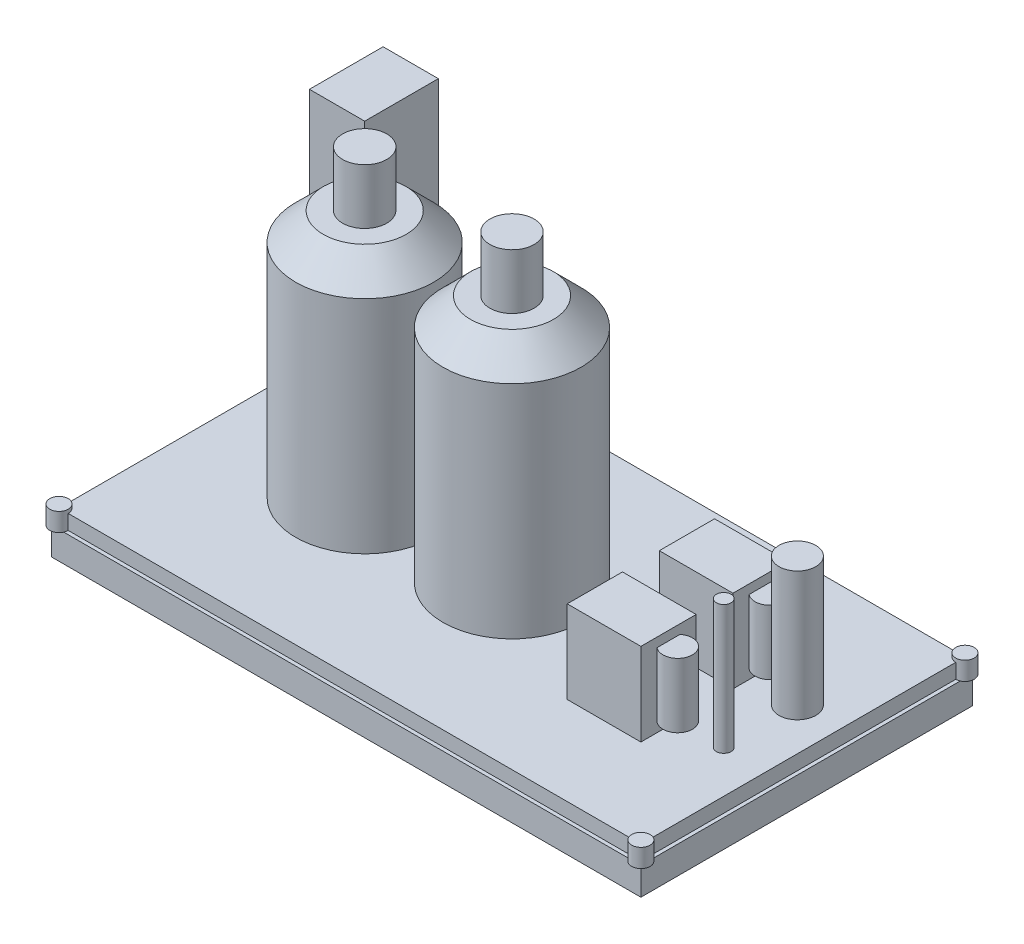
SolidWorks part; units mm, degrees
ref_plane "Front Plane" through (0, 0, 0) normal (0, 0, 1) x (1, 0, 0)
ref_plane "Top Plane" through (0, 0, 0) normal (0, 1, 0) x (1, 0, 0)
ref_plane "Right Plane" through (0, 0, 0) normal (1, 0, 0) x (0, 0, -1)
other "Configuration Table"
sketch "Sketch1" plane through (0, 0, 0) normal (0, 1, 0) x (1, 0, 0)
  line L1 (-1600, -900) -> (1600, -900)
  line L2 (-1600, -900) -> (-1600, 900)
  line L3 (-1600, 900) -> (1600, 900)
  line L4 (1600, -900) -> (1600, 900)
extrude "Boss-Extrude1" add sketch "Sketch1" along normal blind 150
sketch "Sketch2" plane through (0, 0, 0) normal (0, 1, 0) x (1, 0, 0)
  line L1 (-1580, -880) -> (1580, -880)
  line L2 (-1580, -880) -> (-1580, 880)
  line L3 (-1580, 880) -> (1580, 880)
  line L4 (1580, -880) -> (1580, 880)
extrude "Boss-Extrude2" add sketch "Sketch2" along normal blind 80 from offset 150
sketch "Sketch3" plane through (0, 0, 0) normal (0, 1, 0) x (1, 0, 0)
  line L0 (-1600, -900) -> (1600, -900) construction
  line L1 (-800, -900) -> (-600, -900)
  line L2 (-800, -900) -> (-800, 900)
  line L3 (-800, 900) -> (-600, 900)
  line L4 (-600, -900) -> (-600, 900)
  line L5 (1600, 900) -> (-1600, 900) construction
  line L7 (600, -900) -> (800, -900)
  line L8 (600, -900) -> (600, 900)
  line L9 (600, 900) -> (800, 900)
  line L10 (800, -900) -> (800, 900)
extrude "Boss-Extrude3" add sketch "Sketch3" along normal blind 120 from offset 15
sketch "Sketch4" plane through (0, 0, 0) normal (0, 1, 0) x (1, 0, 0)
  circle A0 centre (-800, 0) radius 375
  circle A1 centre (0, 0) radius 375
extrude "Boss-Extrude4" add sketch "Sketch4" along normal blind 1200 from offset 230
sketch "Sketch5" plane through (0, 0, 0) normal (0, 1, 0) x (1, 0, 0)
  circle A0 centre (-800, 0) radius 375
  circle A1 centre (0, 0) radius 375
extrude "Boss-Extrude5" add sketch "Sketch5" along normal blind 150 draft 45 from offset 1430
sketch "Sketch6" plane through (0, 0, 0) normal (0, 1, 0) x (1, 0, 0)
  circle A0 centre (-800, 0) radius 120
  circle A1 centre (0, 0) radius 120
extrude "Boss-Extrude6" add sketch "Sketch6" along normal blind 300 from offset 1580
sketch "Sketch7" plane through (0, 0, 0) normal (0, 1, 0) x (1, 0, 0)
  line L1 (700, -400) -> (1100, -400)
  line L2 (700, -400) -> (700, -100)
  line L3 (700, -100) -> (1100, -100)
  line L4 (1100, -400) -> (1100, -100)
  line L5 (700, 100) -> (1100, 100)
  line L6 (700, 100) -> (700, 400)
  line L7 (700, 400) -> (1100, 400)
  line L8 (1100, 100) -> (1100, 400)
extrude "Boss-Extrude7" add sketch "Sketch7" along normal blind 450 from offset 230
sketch "Sketch8" plane through (0, 0, 0) normal (0, 1, 0) x (1, 0, 0)
  circle A0 centre (1150, -250) radius 80
  circle A1 centre (1150, 250) radius 80
extrude "Boss-Extrude8" add sketch "Sketch8" along normal blind 350 from offset 280
sketch "Sketch9" plane through (0, 0, 0) normal (0, 1, 0) x (1, 0, 0)
  circle A0 centre (1350, 200) radius 100
  circle A1 centre (1350, -200) radius 40
extrude "Boss-Extrude9" add sketch "Sketch9" along normal blind 700 from offset 230
sketch "Sketch10" plane through (0, 0, 0) normal (0, 1, 0) x (1, 0, 0)
  line L1 (-1480, 420) -> (-1430, 420)
  line L2 (-1480, 420) -> (-1480, 470)
  line L3 (-1480, 470) -> (-1430, 470)
  line L4 (-1430, 420) -> (-1430, 470)
  line L5 (-1480, 730) -> (-1430, 730)
  line L6 (-1480, 730) -> (-1480, 780)
  line L7 (-1480, 780) -> (-1430, 780)
  line L8 (-1430, 730) -> (-1430, 780)
extrude "Boss-Extrude10" add sketch "Sketch10" along normal blind 650 from offset 150
sketch "Sketch11" plane through (0, 0, 0) normal (0, 1, 0) x (1, 0, 0)
  line L1 (-1500, 400) -> (-1200, 400)
  line L2 (-1500, 400) -> (-1500, 800)
  line L3 (-1500, 800) -> (-1200, 800)
  line L4 (-1200, 400) -> (-1200, 800)
extrude "Boss-Extrude11" add sketch "Sketch11" along normal blind 800 from offset 800
sketch "Sketch12" plane through (0, 0, 0) normal (0, 1, 0) x (1, 0, 0)
  circle A0 centre (-1580, -880) radius 50
  circle A1 centre (1580, -880) radius 50
  circle A2 centre (-1580, 880) radius 50
  circle A3 centre (1580, 880) radius 50
extrude "Boss-Extrude12" add sketch "Sketch12" along normal blind 100 from offset 150
